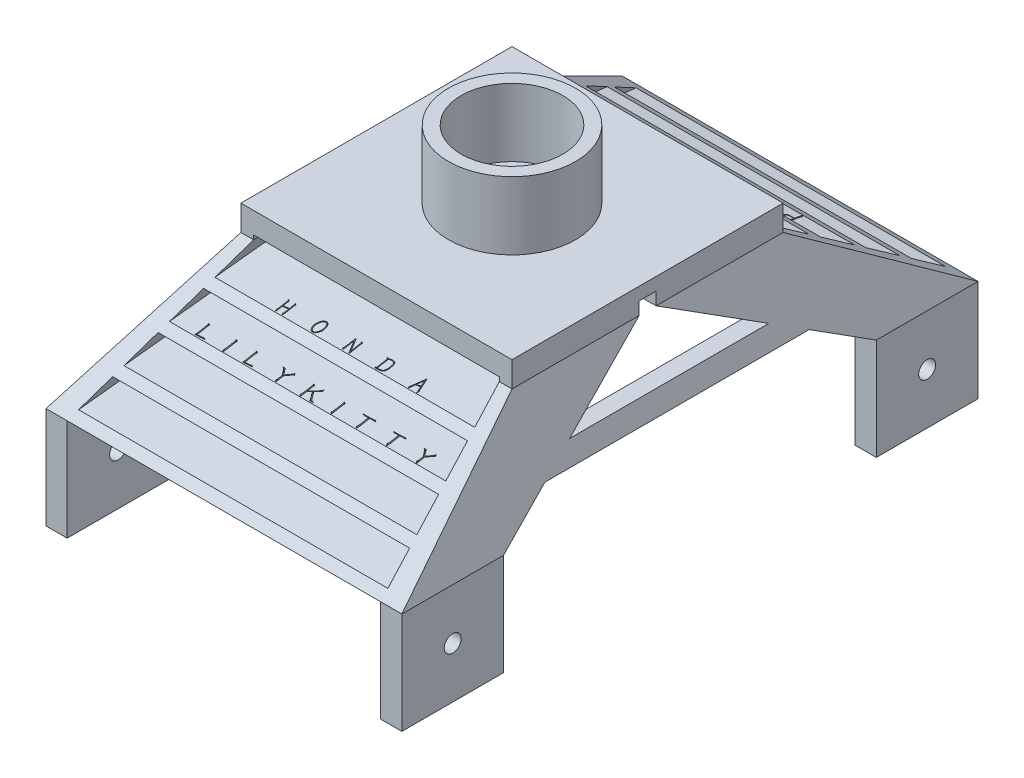
SolidWorks part; units mm, degrees
material "ABS"
ref_plane "前视基准面" through (0, 0, 0) normal (0, 0, 1) x (1, 0, 0)
ref_plane "上视基准面" through (0, 0, 0) normal (0, 1, 0) x (1, 0, 0)
ref_plane "右视基准面" through (0, 0, 0) normal (1, 0, 0) x (0, 0, -1)
other "Configuration Table"
sketch "Sketch4" plane through (0, 0, 0) normal (0, 1, 0) x (1, 0, 0)
  line L0 (0, 0) -> (2.5882, 9.6593) construction
  line L1 (32, -32) -> (-32, -32)
  line L2 (32, -32) -> (32, 32)
  line L3 (32, 32) -> (-32, 32)
  line L4 (-32, -32) -> (-32, 32)
  line L5 (32, -32) -> (-32, 32) construction
  line L6 (32, 32) -> (-32, -32) construction
  line L7 (-2.5882, 9.6593) -> (-2.2, 8.2104)
  line L8 (2.5882, 9.6593) -> (2.2, 8.2104)
  line L9 (-32, 0) -> (32, 0) construction
  line L10 (-2.5882, -9.6593) -> (-2.2, -8.2104)
  line L11 (2.5882, -9.6593) -> (2.2, -8.2104)
  circle A0 centre (0, 0) radius 2.5
  arc A1 (2.5882, 9.6593) -> (-2.5882, 9.6593) centre (0, 0) ccw
  arc A2 (2.2, 8.2104) -> (-2.2, 8.2104) centre (0, 0) ccw
  arc A3 (2.5882, -9.6593) -> (-2.5882, -9.6593) centre (0, 0) cw
  arc A4 (2.2, -8.2104) -> (-2.2, -8.2104) centre (0, 0) cw
  point P0 (0, 0)
  dimension "D3" = 30
  dimension "D1" = 64
  dimension "D2" = 64
extrude "Boss-Extrude3" add sketch "Sketch4" along normal blind 3
sketch "Sketch6" plane through (0, 3, 0) normal (0, 1, 0) x (1, 0, 0)
  circle A0 centre (0, 0) radius 15
  circle A1 centre (0, 0) radius 12
extrude "Boss-Extrude4" add sketch "Sketch6" along normal blind 16
ref_plane "Plane1" through (0, -50, 0) normal (0, 1, 0) x (1, 0, 0)
sketch "Sketch8" plane through (0, -50, 0) normal (0, 1, 0) x (1, 0, 0)
  line L0 (0, -32) -> (0, 32) construction
  line L3 (-32, 0) -> (32, 0) construction
  line L7 (37, -68) -> (42, -68)
  line L8 (37, -68) -> (37, -44)
  line L9 (37, -44) -> (42, -44)
  line L10 (42, -68) -> (42, -44)
  line L18 (-37, -44) -> (-42, -44)
  line L19 (-42, -68) -> (-42, -44)
  line L20 (-37, -68) -> (-42, -68)
  line L21 (-37, -68) -> (-37, -44)
  line L22 (37, 44) -> (42, 44)
  line L23 (42, 68) -> (42, 44)
  line L24 (37, 68) -> (42, 68)
  line L25 (37, 68) -> (37, 44)
  line L26 (-37, 68) -> (-37, 44)
  line L27 (-37, 68) -> (-42, 68)
  line L28 (-42, 68) -> (-42, 44)
  line L29 (-37, 44) -> (-42, 44)
  dimension "D1" = 5
  dimension "D2" = 37
  dimension "D3" = 24
  dimension "D4" = 44
sketch "Sketch12" plane through (0, 0, 0) normal (0, -1, 0) x (1, 0, 0)
  line L0 (-32, 0) -> (32, 0) construction
  line L1 (32, 32) -> (29, 32)
  line L2 (32, 32) -> (32, 2)
  line L3 (32, 2) -> (29, 2)
  line L4 (29, 32) -> (29, 2)
  line L5 (-32, -32) -> (-32, 32) construction
  line L6 (32, 32) -> (32, -32) construction
  line L7 (0, 32) -> (0, -32) construction
  line L8 (-32, 32) -> (32, 32) construction
  line L9 (32, -32) -> (-32, -32) construction
  line L10 (32, -2) -> (29, -2)
  line L11 (29, -32) -> (29, -2)
  line L12 (32, -32) -> (29, -32)
  line L13 (32, -32) -> (32, -2)
  line L14 (-32, 2) -> (-29, 2)
  line L15 (-29, 32) -> (-29, 2)
  line L16 (-32, 32) -> (-29, 32)
  line L17 (-32, 32) -> (-32, 2)
  line L18 (-32, -32) -> (-32, -2)
  line L19 (-32, -32) -> (-29, -32)
  line L20 (-29, -32) -> (-29, -2)
  line L21 (-32, -2) -> (-29, -2)
  dimension "D1" = 3
  dimension "D2" = 30
extrude "Boss-Extrude7" add sketch "Sketch8" along normal blind 24 separate body
sketch "Sketch16" plane through (0, 0, 0) normal (1, 0, 0) x (0, 0, -1)
  line L0 (-68, -26) -> (-68, -50) construction
  line L1 (68, -26) -> (68, -50) construction
  circle A0 centre (-56, -38) radius 2
  circle A1 centre (56, -38) radius 2
  dimension "D1" = 12
  dimension "D2" = 12
extrude "Cut-Extrude3" cut sketch "Sketch16" against normal blind 85
extrude "Cut-Extrude4" cut sketch "Sketch16<2>" along normal blind 114
sketch "Sketch16<2>" plane through (0, 0, 0) normal (1, 0, 0) x (0, 0, -1) same geometry as "Sketch16"
extrude "Boss-Extrude8" add sketch "Sketch12" along normal blind 3
loft "Loft4" add section face at (-30.5, -3, -17) section face at (-39.5, -26, -56) connector at (-29, -3, -32) connector at (-37, -26, -68)
loft "Loft5" add section face at (-30.5, -3, 17) section face at (-39.5, -26, 56) connector at (-32, -3, 32) connector at (-42, -26, 68)
loft "Loft6" add section face at (30.5, -3, -17) section face at (39.5, -26, -56) connector at (32, -3, -32) connector at (42, -26, -68)
loft "Loft7" add section face at (30.5, -3, 17) section face at (39.5, -26, 56) connector at (29, -3, 32) connector at (37, -26, 68)
sketch "Sketch23" plane through (0, 0, 0) normal (0, -1, 0) x (1, 0, 0)
  line L0 (29, 32) -> (29, 2) construction
  line L1 (-29, 32) -> (29, 32)
  line L2 (-29, 32) -> (-29, 30)
  line L3 (-29, 30) -> (29, 30)
  line L4 (29, 32) -> (29, 30)
  line L5 (-32, 0) -> (32, 0) construction
  line L6 (-32, -2) -> (-32, 2) construction
  line L7 (32, 2) -> (32, -2) construction
  line L8 (-29, 2) -> (-29, 32) construction
  line L9 (-29, 22) -> (29, 22)
  line L10 (-29, 22) -> (-29, 20)
  line L11 (-29, 20) -> (29, 20)
  line L12 (29, 22) -> (29, 20)
  line L13 (-29, -10) -> (29, -10)
  line L14 (-29, 12) -> (29, 12)
  line L15 (-29, 12) -> (-29, 10)
  line L16 (-29, 10) -> (29, 10)
  line L17 (29, 12) -> (29, 10)
  line L18 (29, -12) -> (29, -10)
  line L19 (-29, -12) -> (29, -12)
  line L20 (-29, -12) -> (-29, -10)
  line L21 (-29, -20) -> (29, -20)
  line L22 (29, -22) -> (29, -20)
  line L23 (-29, -22) -> (29, -22)
  line L24 (-29, -22) -> (-29, -20)
  line L25 (-29, -30) -> (29, -30)
  line L26 (29, -32) -> (29, -30)
  line L27 (-29, -32) -> (29, -32)
  line L28 (-29, -32) -> (-29, -30)
  dimension "D1" = 2
  dimension "D2" = 2
  dimension "D3" = 8
  dimension "D4" = 2
  dimension "D5" = 8
extrude "Boss-Extrude14" add sketch "Sketch23" along normal blind 2
sketch "Sketch30" plane through (0, 0, 0) normal (1, 0, 0) x (0, 0, -1)
  line L0 (-17, -3) -> (-56, -26) construction
  line L1 (-2, -3) -> (-32, -3) construction
  line L2 (-68, -26) -> (-44, -26) construction
  line L3 (-68, -26) -> (-50.8819, -22.9816)
  line L4 (-65.8048, -24.5975) -> (-48.4257, -21.5331)
  line L5 (-32, -3) -> (-68, -26) construction
  line L6 (-41.0571, -17.1875) -> (-59.2191, -20.39)
  line L7 (-38.6009, -15.739) -> (-57.0239, -18.9875)
  line L8 (-31.2324, -11.3935) -> (-50.4382, -14.78)
  line L9 (-28.7762, -9.9449) -> (-48.243, -13.3775)
  line L10 (-21.4077, -5.5994) -> (-41.6573, -9.17)
  line L11 (-18.9515, -4.1509) -> (-39.4621, -7.7675)
  line L12 (-65.8048, -24.5975) -> (-68, -26)
  line L13 (-48.4257, -21.5331) -> (-50.8819, -22.9816)
  line L14 (-18.9515, -4.1509) -> (-21.4077, -5.5994)
  line L15 (-39.4621, -7.7675) -> (-41.6573, -9.17)
  line L16 (-48.243, -13.3775) -> (-50.4382, -14.78)
  line L17 (-57.0239, -18.9875) -> (-59.2191, -20.39)
  line L18 (-38.6009, -15.739) -> (-41.0571, -17.1875)
  line L19 (-28.7762, -9.9449) -> (-31.2324, -11.3935)
  dimension "D1" = 10
  dimension "D2" = 1
  dimension "D3" = 3
  dimension "D4" = 1
  dimension "D5" = 3
  dimension "D6" = 1
  dimension "D7" = 3
  dimension "D8" = 1
extrude "Boss-Extrude19" add sketch "Sketch30" along normal blind 45 and the other way blind 47
sketch "Sketch31" plane through (0, 0, 0) normal (0, 0, 1) x (1, 0, 0)
  line L0 (-32, -3) -> (-42, -26)
  line L1 (-42, -26) -> (-54.1068, -26)
  line L2 (-54.1068, -26) -> (-54.1068, -3)
  line L3 (-54.1068, -3) -> (-32, -3)
  line L4 (32, -3) -> (50.2676, -3)
  line L5 (50.2676, -3) -> (50.2676, -26)
  line L6 (50.2676, -26) -> (42, -26)
  line L7 (42, -26) -> (32, -3)
extrude "Cut-Extrude9" cut sketch "Sketch31" along normal blind 95
mirror "Mirror7" about plane through (0, 0, 0) normal (0, 0, 1) of "Cut-Extrude9", "Boss-Extrude19"
sketch "Sketch32" plane through (0, 0, 0) normal (0, 0, 1) x (1, 0, 0)
  line L22 (34.5609, -18.9875) -> (38.9511, -18.9875)
  line L23 (-34.5609, -18.9875) -> (34.5609, -18.9875) construction
  line L24 (33.0974, -14.78) -> (34.5609, -18.9875) construction
  line L25 (32, -3) -> (42, -26) construction
  line L26 (34.5609, -18.9875) -> (33.0974, -14.78)
  line L27 (33.0974, -14.78) -> (37.1217, -14.78)
  line L28 (37.1217, -14.78) -> (38.9511, -18.9875)
extrude "Boss-Extrude21" add sketch "Sketch32" along normal blind 44 and the other way blind 37
mirror "Mirror8" about plane through (0, 0, 0) normal (1, 0, 0) of "Boss-Extrude21"
ref_plane "Plane2" through (0, -15, 0) normal (0, 1, 0) x (1, 0, 0)
sketch "Sketch34" plane through (0, -15, 0) normal (0, 1, 0) x (1, 0, 0)
  line L0 (-32, 0) -> (49968, 0) construction
  line L3 (-32, 2) -> (-32, -2) construction
  line L8 (32, -2) -> (32, 2) construction
  line L10 (-9, -10) -> (-5, -10)
  line L11 (-9, -10) -> (-9, 10)
  line L12 (-9, 10) -> (-5, 10)
  line L13 (-5, -10) -> (-5, 10)
  line L14 (-9, -10) -> (-5, 10) construction
  line L15 (-9, 10) -> (-5, -10) construction
  point P4 (-32, 0)
  point P7 (32, 0)
  point P8 (-7, 0)
  point P14 (-5, 0)
  dimension "D1" = 5
  dimension "D2" = 4
  dimension "D3" = 20
extrude "Boss-Extrude23" add sketch "Sketch34" against normal blind 25
extrude "Boss-Extrude24" add sketch "Sketch34<2>" along normal blind 17 and the other way blind 30
sketch "Sketch34<2>" plane through (0, -15, 0) normal (0, 1, 0) x (1, 0, 0) same geometry as "Sketch34"
sketch "Sketch35" plane through (0, -0.7848, -0.1384) normal (0, 0.9848, 0.1736) x (1, 0, 0)
  text T0 "HONDA" font "汉仪长仿宋体" height 3.5
extrude "Cut-Extrude10" cut sketch "Sketch35" against normal blind 1
sketch "Sketch36" plane through (0, -4.724, -0.833) normal (0, 0.9848, 0.1736) x (1, 0, 0)
  text T0 "LILYKITTY" font "汉仪长仿宋体" height 3.5
extrude "Cut-Extrude11" cut sketch "Sketch36" against normal blind 1
sketch "Sketch38" plane through (0, -0.7848, 0.1384) normal (0, 0.9848, -0.1736) x (1, 0, 0)
  text T0 "PiSQUAD" font "汉仪长仿宋体" height 3.5
extrude "Cut-Extrude12" cut sketch "Sketch38" against normal blind 1
sketch "Sketch39" plane through (0, -4.724, 0.833) normal (0, 0.9848, -0.1736) x (1, 0, 0)
  text T0 "PIONNER" font "汉仪长仿宋体" height 3.5
extrude "Cut-Extrude13" cut sketch "Sketch39" against normal blind 1
